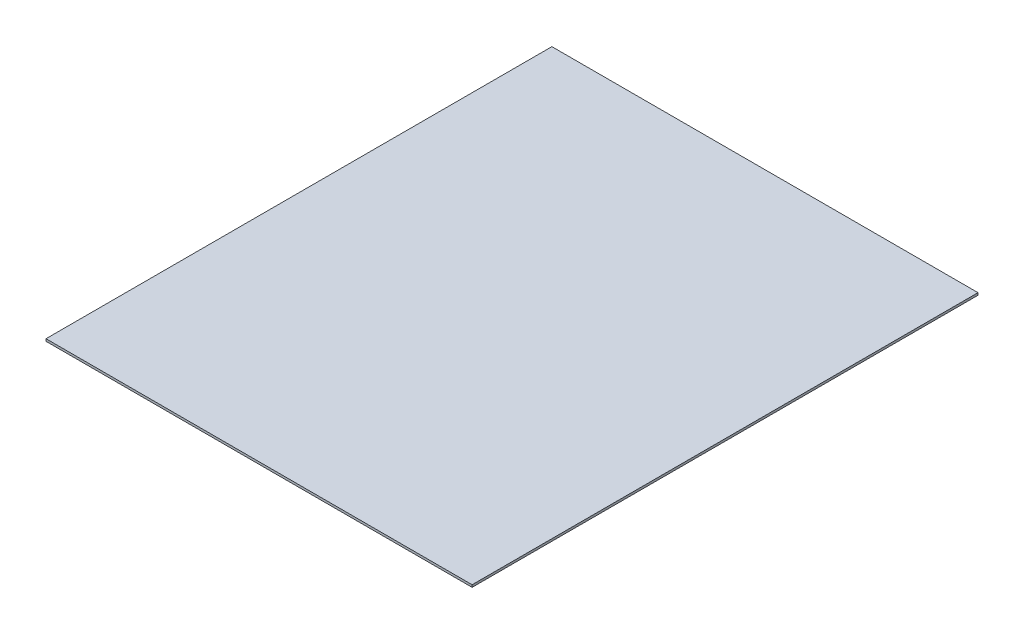
SolidWorks part; units mm, degrees
ref_plane "Front Plane" through (0, 0, 0) normal (0, 0, 1) x (1, 0, 0)
ref_plane "Top Plane" through (0, 0, 0) normal (0, 1, 0) x (1, 0, 0)
ref_plane "Right Plane" through (0, 0, 0) normal (1, 0, 0) x (0, 0, -1)
sketch "Sketch1" plane through (0, 0, 0) normal (0, 1, 0) x (1, 0, 0)
  line L1 (-56.1029, 186.4626) -> (130.8971, 186.4626)
  line L2 (-56.1029, 186.4626) -> (-56.1029, -35.5374)
  line L3 (-56.1029, -35.5374) -> (130.8971, -35.5374)
  line L4 (130.8971, 186.4626) -> (130.8971, -35.5374)
  dimension "D1" = 187
  dimension "D2" = 222
extrude "Boss-Extrude1" add sketch "Sketch1" along normal blind 1
